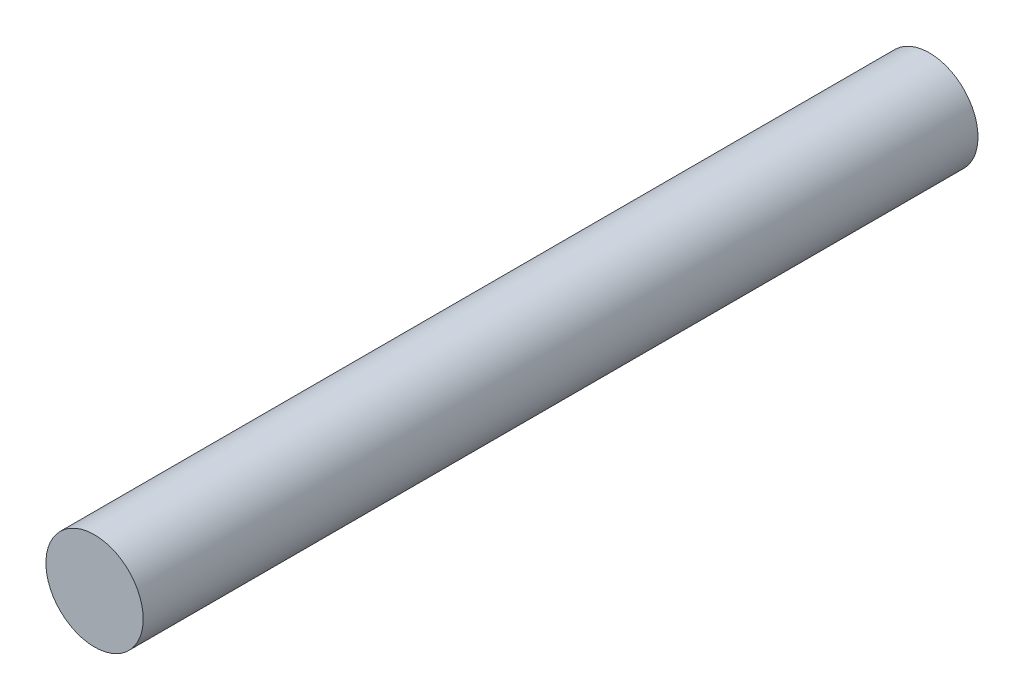
SolidWorks part; units mm, degrees
ref_plane "Front Plane" through (0, 0, 0) normal (0, 0, 1) x (1, 0, 0)
ref_plane "Top Plane" through (0, 0, 0) normal (0, 1, 0) x (1, 0, 0)
ref_plane "Right Plane" through (0, 0, 0) normal (1, 0, 0) x (0, 0, -1)
sketch "Sketch1" plane through (0, 0, 0) normal (0, 0, 1) x (1, 0, 0)
  circle A0 centre (0, 0) radius 2
  dimension "D1" = 4
extrude "Boss-Extrude1" add sketch "Sketch1" along normal blind 34.3306
sketch "Sketch2" plane through (0, 0, 0) normal (0, 0, -1) x (-1, 0, 0)
  point P0 (0, 0)
